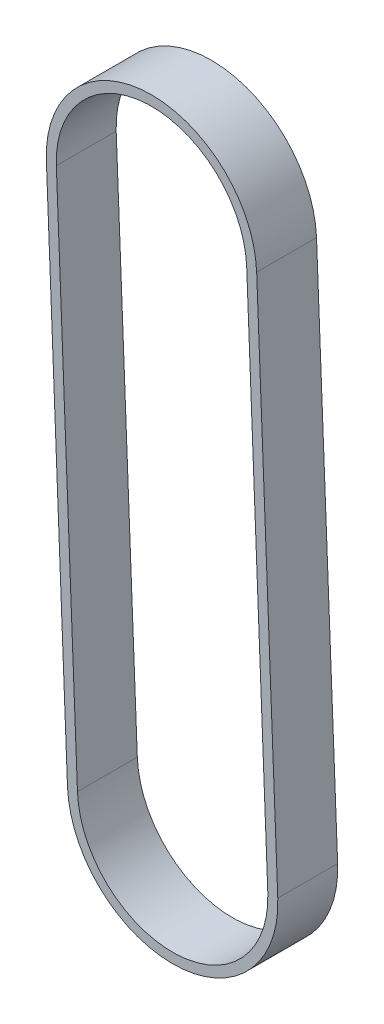
SolidWorks part; units mm, degrees
ref_plane "Front Plane" through (0, 0, 0) normal (0, 0, 1) x (1, 0, 0)
ref_plane "Top Plane" through (0, 0, 0) normal (0, 1, 0) x (1, 0, 0)
ref_plane "Right Plane" through (0, 0, 0) normal (1, 0, 0) x (0, 0, -1)
sketch "Sketch2" plane through (0, 0, 0) normal (0, 0, 1) x (1, 0, 0)
  line L0 (0, 0) -> (1, 0) construction
  line L1 (0, 0) -> (0, 1) construction
  line L4 (14.2939, 0.5954) -> (17.4689, -79.3416)
  line L5 (-11.1564, -80.4785) -> (-14.3314, -0.5416)
  arc A0 (-14.3314, -0.5416) -> (14.2939, 0.5954) centre (-0.0187, 0.0269) cw
  arc A2 (17.4689, -79.3416) -> (-11.1564, -80.4785) centre (3.1563, -79.9101) cw
extrude "Extrude-Thin1" add sketch "Sketch2" against normal blind 9 thin thin type one direction wall 1.5
